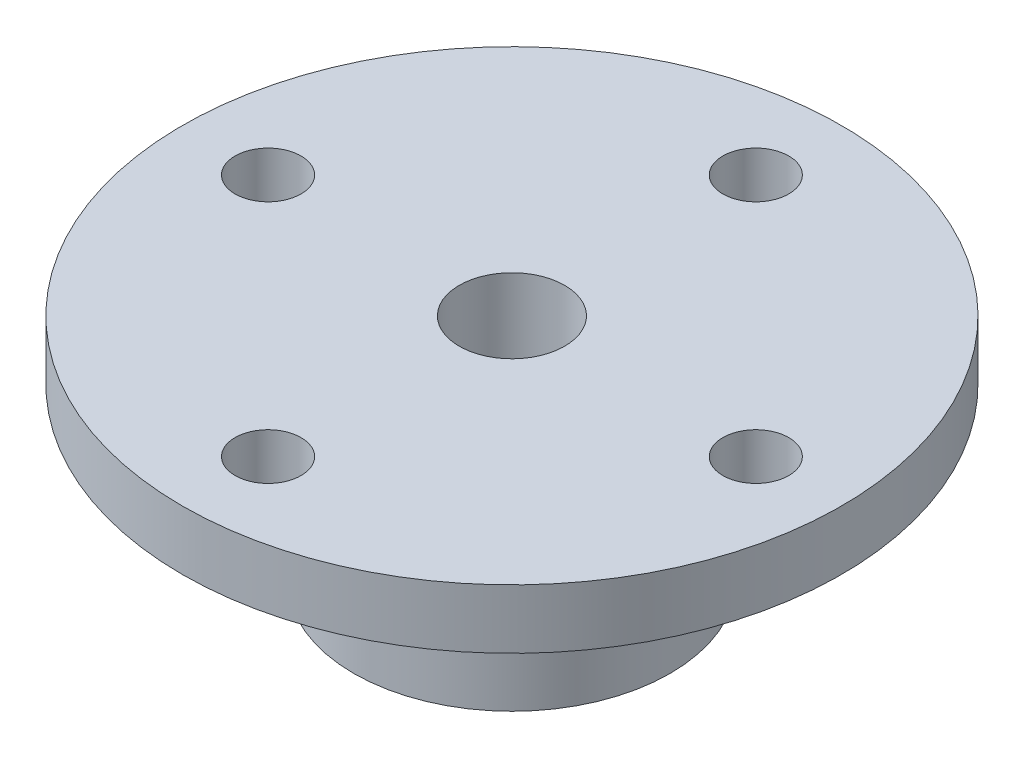
SolidWorks part; units mm, degrees
ref_plane "前视基准面" through (0, 0, 0) normal (0, 0, 1) x (1, 0, 0)
ref_plane "上视基准面" through (0, 0, 0) normal (0, 1, 0) x (1, 0, 0)
ref_plane "右视基准面" through (0, 0, 0) normal (1, 0, 0) x (0, 0, -1)
other "Configuration Table"
sketch "草图1" plane through (0, 0, 0) normal (0, 1, 0) x (1, 0, 0)
  circle A0 centre (0, 0) radius 12
  circle A1 centre (0, 0) radius 4
  dimension "D1" = 8
  dimension "D2" = 24
extrude "凸台-拉伸1" add sketch "草图1" along normal blind 13
sketch "草图2" plane through (0, 13, 0) normal (0, 1, 0) x (1, 0, 0)
  circle A0 centre (0, 0) radius 25
  circle A1 centre (0, 0) radius 4
  circle A2 centre (0, 0) radius 18.5
  circle A3 centre (0, 18.5) radius 2.5
  circle A4 centre (-18.5, 0) radius 2.5
  circle A5 centre (18.5, 0) radius 2.5
  circle A6 centre (0, -18.5) radius 2.5
  point P13 (0, -18.5)
  circle M1 centre (0, 0) radius 12
  circle M2 centre (0, 0) radius 4
  dimension "D1" = 8
  dimension "D2" = 50
  dimension "D3" = 37
  dimension "D4" = 5
  dimension "D5" = 5
  dimension "D6" = 5
  dimension "D7" = 5
extrude "凸台-拉伸2" add sketch "草图2" along normal blind 4.5 contours A0 A6 A2 A4 A3 A5 | A6 A2 A5 A3 A4 M1 | M1 M2 region at (-24.2929, 13, 0) region at (15.4815, 13, 0) region at (-11.6606, 13, 0)
